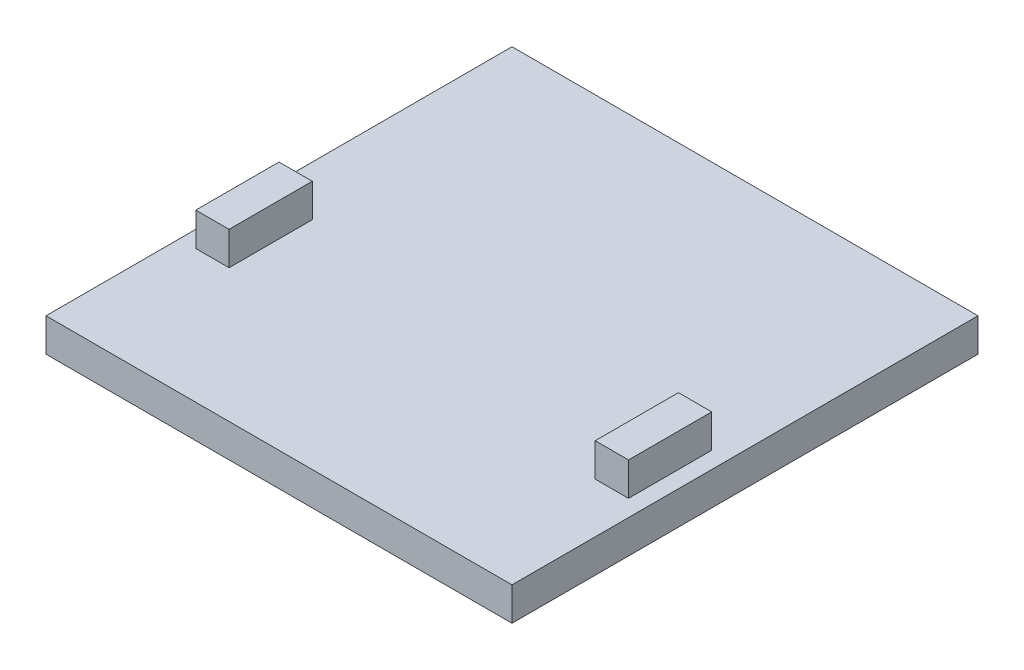
SolidWorks part; units mm, degrees
ref_plane "Front Plane" through (0, 0, 0) normal (0, 0, 1) x (1, 0, 0)
ref_plane "Top Plane" through (0, 0, 0) normal (0, 1, 0) x (1, 0, 0)
ref_plane "Right Plane" through (0, 0, 0) normal (1, 0, 0) x (0, 0, -1)
sketch "Sketch1" plane through (0, 0, 0) normal (0, 1, 0) x (1, 0, 0)
  line L1 (-355.6, -355.6) -> (355.6, -355.6)
  line L2 (-355.6, -355.6) -> (-355.6, 355.6)
  line L3 (-355.6, 355.6) -> (355.6, 355.6)
  line L4 (355.6, -355.6) -> (355.6, 355.6)
  line L5 (-355.6, -355.6) -> (355.6, 355.6) construction
  line L6 (-355.6, 355.6) -> (355.6, -355.6) construction
  point P0 (0, 0)
  dimension "D1" = 711.2
  dimension "D2" = 711.2
extrude "Boss-Extrude1" add sketch "Sketch1" along normal blind 50.8
sketch "Sketch2" plane through (0, 50.8, 0) normal (0, 1, 0) x (1, 0, 0)
  line L0 (355.6, -355.6) -> (355.6, 355.6) construction
  line L1 (330.2, -152.4) -> (279.4, -152.4)
  line L2 (330.2, -152.4) -> (330.2, -25.4)
  line L3 (330.2, -25.4) -> (279.4, -25.4)
  line L4 (279.4, -152.4) -> (279.4, -25.4)
  line L5 (0, -355.6) -> (0, 355.6) construction
  line L6 (-355.6, -355.6) -> (355.6, -355.6) construction
  line L7 (355.6, 355.6) -> (-355.6, 355.6) construction
  line L8 (-330.2, -152.4) -> (-330.2, -25.4)
  line L9 (-330.2, -152.4) -> (-279.4, -152.4)
  line L10 (-279.4, -152.4) -> (-279.4, -25.4)
  line L11 (-330.2, -25.4) -> (-279.4, -25.4)
  dimension "D1" = 50.8
  dimension "D2" = 127
  dimension "D3" = 25.4
  dimension "D4" = 203.2
extrude "Boss-Extrude2" add sketch "Sketch2" along normal blind 50.8
